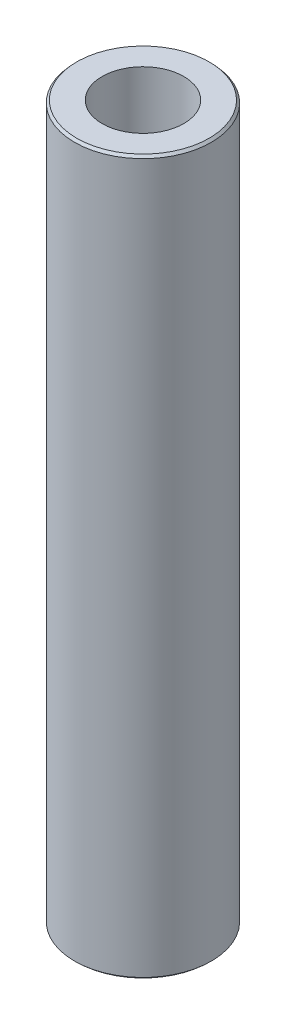
SolidWorks part; units mm, degrees
ref_plane "Front Plane" through (0, 0, 0) normal (0, 0, 1) x (1, 0, 0)
ref_plane "Top Plane" through (0, 0, 0) normal (0, 1, 0) x (1, 0, 0)
ref_plane "Right Plane" through (0, 0, 0) normal (1, 0, 0) x (0, 0, -1)
sketch "Sketch1" plane through (0, 0, 0) normal (0, 1, 0) x (1, 0, 0)
  circle A0 centre (0, 0) radius 57.5
  dimension "SHAFT_OD" = 115
extrude "Boss-Extrude1" add sketch "Sketch1" along normal blind 600
sketch "Sketch2" plane through (0, 0, 0) normal (0, 1, 0) x (1, 0, 0)
  circle A0 centre (0, 0) radius 34.3367
  dimension "BORE_D" = 68.6734
extrude "Cut-Extrude1" cut sketch "Sketch2" along normal through all
chamfer "Chamfer1" distance 2.0403 angle 42.129 2 edges at (0, 600, 57.5) (0, 0, 57.5) first distance on face at (0, 600, 57.5) first distance on face at (0, 0, 34.3367)
